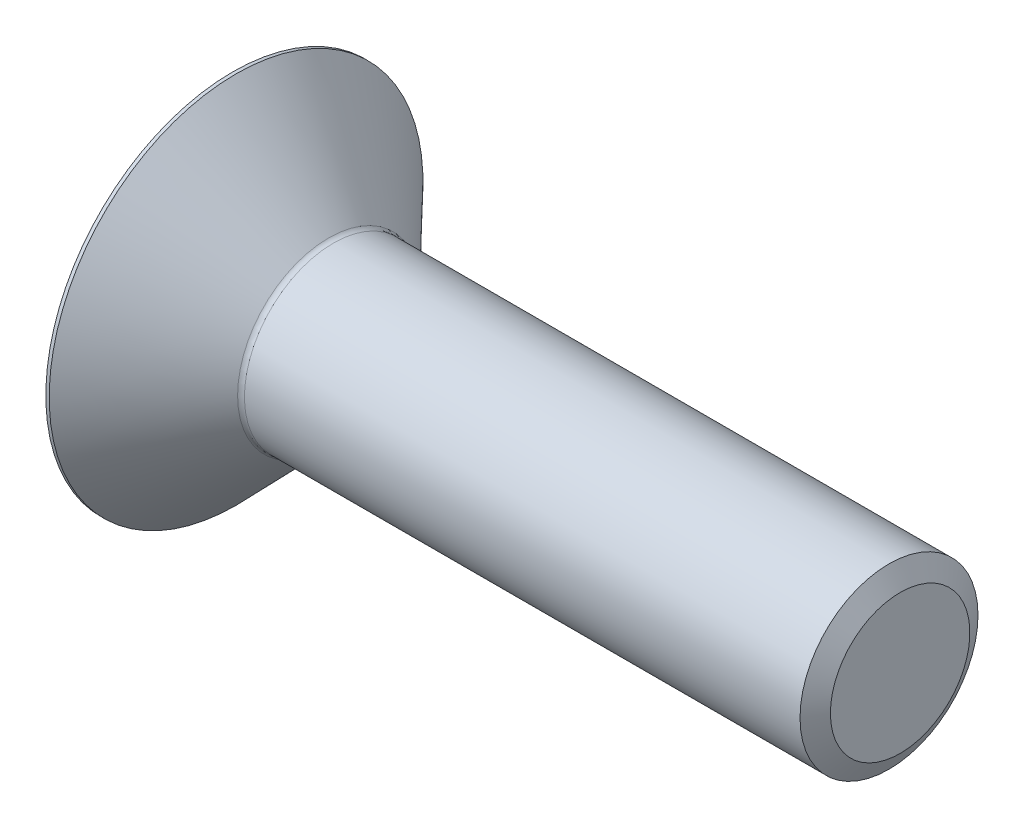
SolidWorks part; units mm, degrees
ref_plane "前视基准面" through (0, 0, 0) normal (0, 0, 1) x (1, 0, 0)
ref_plane "上视基准面" through (0, 0, 0) normal (0, 1, 0) x (1, 0, 0)
ref_plane "右视基准面" through (0, 0, 0) normal (1, 0, 0) x (0, 0, -1)
sketch "尺寸草图" plane through (0, 0, 0) normal (0, 0, 1) x (1, 0, 0)
  line L0 (0, 0) -> (60, 0) construction
  line L1 (60, 0) -> (60, 8) construction
  line L2 (60, 8) -> (58, 8) construction
  line L3 (58, 8) -> (16, 8) construction
  line L4 (0, 16.8) -> (8.8, 16.8) construction
  line L5 (8.8, 16.8) -> (9.4, 16.8) construction
  point P3 (60, 8.75)
  point P7 (0, 16.8)
  point P8 (0, 8)
  point P9 (0, 11.43)
  point P13 (0, 5)
  point P15 (4.8, 16.8)
  point P16 (7.2, 16.8)
  dimension "l" = 60
  dimension "d" = 16
  dimension "P" = 2
  dimension "b" = 44
  dimension "da" = 17.5
  dimension "dk" = 33.6
  dimension "ds" = 16
  dimension "e" = 11.43
  dimension "k" = 8.8
  dimension "r" = 0.6
  dimension "s" = 10
  dimension "t" = 4.8
  dimension "w" = 2.2
sketch "草图1" plane through (0, 0, 0) normal (0, 0, 1) x (1, 0, 0)
  line L0 (0, 8) -> (-50.9453, 8)
  line L1 (-51.3769, 8.1832) -> (-59.6981, 16.8)
  line L2 (-59.6981, 16.8) -> (-60, 16.8)
  line L3 (-60, 16.8) -> (-60, 0)
  line L4 (-60, 0) -> (0, 0)
  line L5 (0, 0) -> (0, 8)
  line L6 (0, 0) -> (-60, 0) construction
  arc A0 (-50.9453, 8) -> (-51.3769, 8.1832) centre (-50.9453, 8.6) cw
  point P9 (-51.2, 8)
  dimension "r" = 0.6
  dimension "k" = 8.8
  dimension "dk" = 33.6
  dimension "l" = 60
  dimension "D5" = 46
  dimension "d" = 16
revolve "旋转1" add sketch "草图1" angle 360 about L6
cosmetic thread "装饰螺纹线1" parameters "b"=44, "D2"=12.8
sketch "草图2" plane through (-60, 0, 0) normal (-1, 0, 0) x (0, 0, 1)
  line L0 (0, 0) -> (0, 8) construction
  line L1 (0, 5.7735) -> (-5, 2.8868)
  line L2 (-5, 2.8868) -> (-5, -2.8868)
  line L3 (-5, -2.8868) -> (0, -5.7735)
  line L4 (0, -5.7735) -> (5, -2.8868)
  line L5 (5, -2.8868) -> (5, 2.8868)
  line L6 (5, 2.8868) -> (0, 5.7735)
  circle A0 centre (0, 0) radius 5 construction
  point P1 (0, 5.6565)
  dimension "s" = 10
  dimension "e" = 11.43
extrude "切除-拉伸1" cut sketch "草图2" against normal blind 8.8
sketch "草图6" plane through (0, 0, 0) normal (0, 0, 1) x (1, 0, 0)
  line L0 (-55.2, 5.7735) -> (-51.8667, 0)
  line L1 (-51.8667, 0) -> (-49.77, 0)
  line L2 (-49.77, 0) -> (-49.77, 5.7735)
  line L3 (-49.77, 5.7735) -> (-55.2, 5.7735)
  line L4 (-60, 0) -> (-51.2, 0) construction
  line L5 (-60, 0) -> (-71.43, 0) construction
  dimension "D1" = 60
  dimension "t" = 4.8
  dimension "t1" = 8.8
  dimension "e-s" = 1.43
  dimension "e" = 11.43
revolve "旋转2" add sketch "草图6" angle 360 about L4
sketch "草图7" plane through (0, 0, 0) normal (0, 0, 1) x (1, 0, 0)
  line L0 (-60, 5.7735) -> (-60, 0)
  line L1 (-60, 0) -> (-58.57, 0)
  line L2 (-58.57, 0) -> (-60, 5.7735)
  line L3 (-60, 0) -> (-58.57, 0) construction
  dimension "e-s*1.1" = 1.43
revolve "切除-旋转2" cut sketch "草图7" angle 360 about L3
sketch "草图4" plane through (0, 0, 0) normal (0, 0, 1) x (1, 0, 0)
  line L0 (-1, 8) -> (0, 6.2679)
  line L1 (0, -8) -> (0, 8) construction
  line L2 (0, 6.2679) -> (1, 8)
  line L3 (1, 8) -> (-1, 8)
  line L4 (-1, 0) -> (1, 0) construction
  dimension "d" = 16
  dimension "p" = 2
revolve "切除-旋转1" cut sketch "草图4" angle 360 about L4
ref_axis "基准轴1" through (-21.1715, 0, 0) along (1, 0, 0)
pattern_linear "阵列(线性)2" [suppressed] count 22 spacing 2 along (-1, 0, 0) of bodies 104
ref_plane "基准面1" through (-50.9453, 0, 0) normal (1, 0, 0) x (0, 0, -1)
